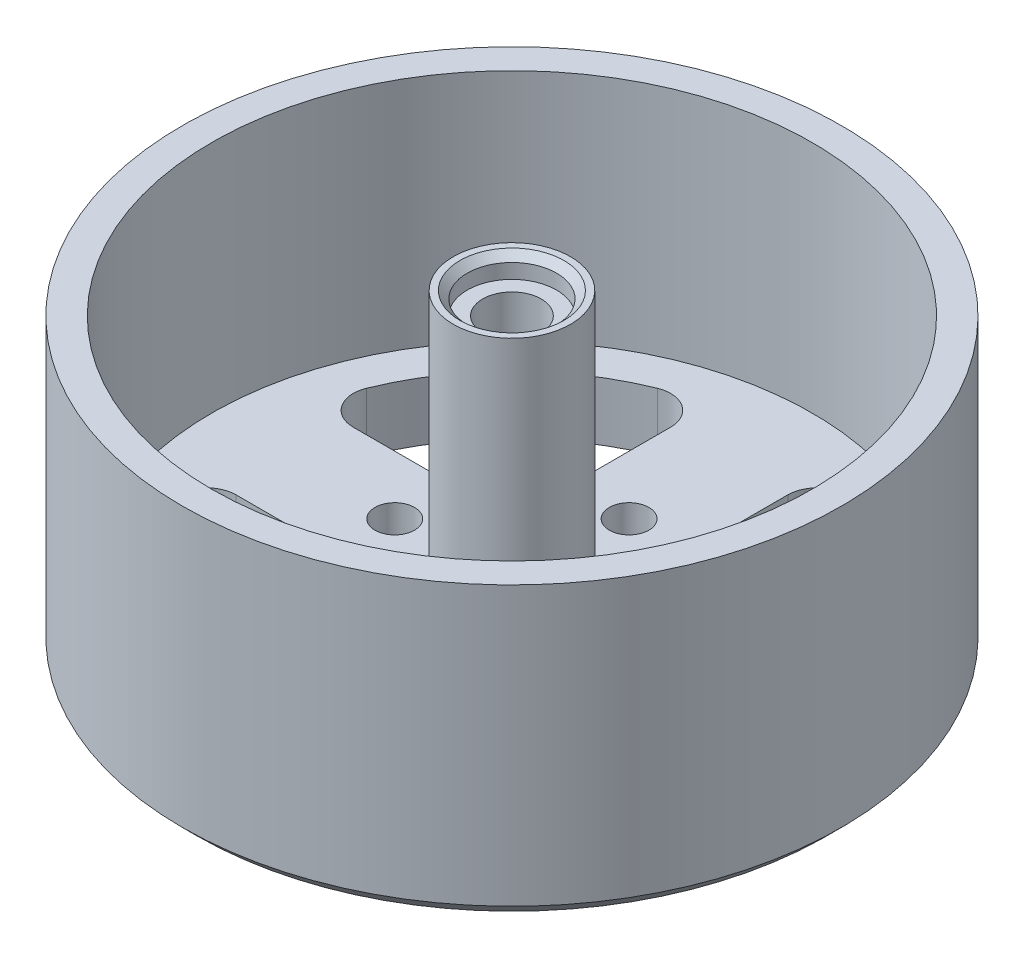
SolidWorks part; units mm, degrees
material "三聚氰胺甲醛树脂"
ref_plane "前视基准面" through (0, 0, 0) normal (0, 0, 1) x (1, 0, 0)
ref_plane "上视基准面" through (0, 0, 0) normal (0, 1, 0) x (1, 0, 0)
ref_plane "右视基准面" through (0, 0, 0) normal (1, 0, 0) x (0, 0, -1)
sketch "草图1" plane through (0, 0, 0) normal (0, 1, 0) x (1, 0, 0)
  line L0 (-17.5499, 4) -> (-4, 4)
  line L1 (-4, 4) -> (-4, 17.5499)
  line L2 (4, 17.5499) -> (4, 4)
  line L3 (4, 4) -> (17.5499, 4)
  line L4 (17.5499, -4) -> (4, -4)
  line L5 (4, -4) -> (4, -17.5499)
  line L6 (-4, -17.5499) -> (-4, -4)
  line L7 (-4, -4) -> (-17.5499, -4)
  circle A0 centre (0, 0) radius 2
  circle A1 centre (0, 0) radius 20.5
  circle A2 centre (0, 0) radius 22.5
  circle A3 centre (0, 0) radius 4
  circle A4 centre (-8, 0) radius 1.35
  circle A5 centre (0, 8) radius 1.35
  circle A6 centre (8, 0) radius 1.35
  circle A7 centre (0, -8) radius 1.35
  arc A8 (-4, 17.5499) -> (-17.5499, 4) centre (0, 0) ccw
  arc A9 (17.5499, 4) -> (4, 17.5499) centre (0, 0) ccw
  arc A10 (-17.5499, -4) -> (-4, -17.5499) centre (0, 0) ccw
  arc A11 (4, -17.5499) -> (17.5499, -4) centre (0, 0) ccw
  point P17 (0, 0)
  point P31 (0, 0)
  dimension "D1" = 8
  dimension "D2" = 4
  dimension "D3" = 41
  dimension "D4" = 45
  dimension "D5" = 2.7
  dimension "D6" = 8
  dimension "D8" = 36
  dimension "D10" = 8
  dimension "D7" = 4
  dimension "D9" = 4
extrude "凸台-拉伸1" add sketch "草图1" along normal blind 4 contours A1 A11 L5 L4 A10 L7 L6 A9 L3 L2 A8 L1 L0 A7 A6 A5 A4 A3 region at (-19.9202, 0, 0)
extrude "凸台-拉伸2" add sketch "草图1<3>" along normal blind 20 contours A3 A0 region at (-3.8869, 0, 0)
sketch "草图1<3>" plane through (0, 0, 0) normal (0, 1, 0) x (1, 0, 0) same geometry as "草图1"
extrude "凸台-拉伸3" add sketch "草图1<4>" along normal blind 20 contours A2 A1 region at (-21.8636, 0, 0)
sketch "草图1<4>" plane through (0, 0, 0) normal (0, 1, 0) x (1, 0, 0) same geometry as "草图1"
fillet "圆角1" radius 5 4 edges at (-4, 2, 4) (4, 2, 4) (4, 2, -4) (-4, 2, -4)
fillet "圆角2" radius 2 8 edges at (4, 2, 17.5499) (17.5499, 2, 4) (17.5499, 2, -4) (4, 2, -17.5499) (-4, 2, 17.5499) (-17.5499, 2, 4) (-4, 2, -17.5499) (-17.5499, 2, -4)
chamfer "倒角1" distance 1 angle 45 1 edges at (0, 0, 22.5)
sketch "草图2" plane through (0, 20, 0) normal (0, 1, 0) x (1, 0, 0)
  circle A0 centre (0, 0) radius 4 construction
  circle A1 centre (0, 0) radius 4
  circle A2 centre (0, 0) radius 3.05
  dimension "D1" = 6.1
extrude "凸台-拉伸4" add sketch "草图2" along normal blind 1.5
chamfer "倒角2" distance 0.5 angle 45 1 edges at (0, 21.5, 3.05)
